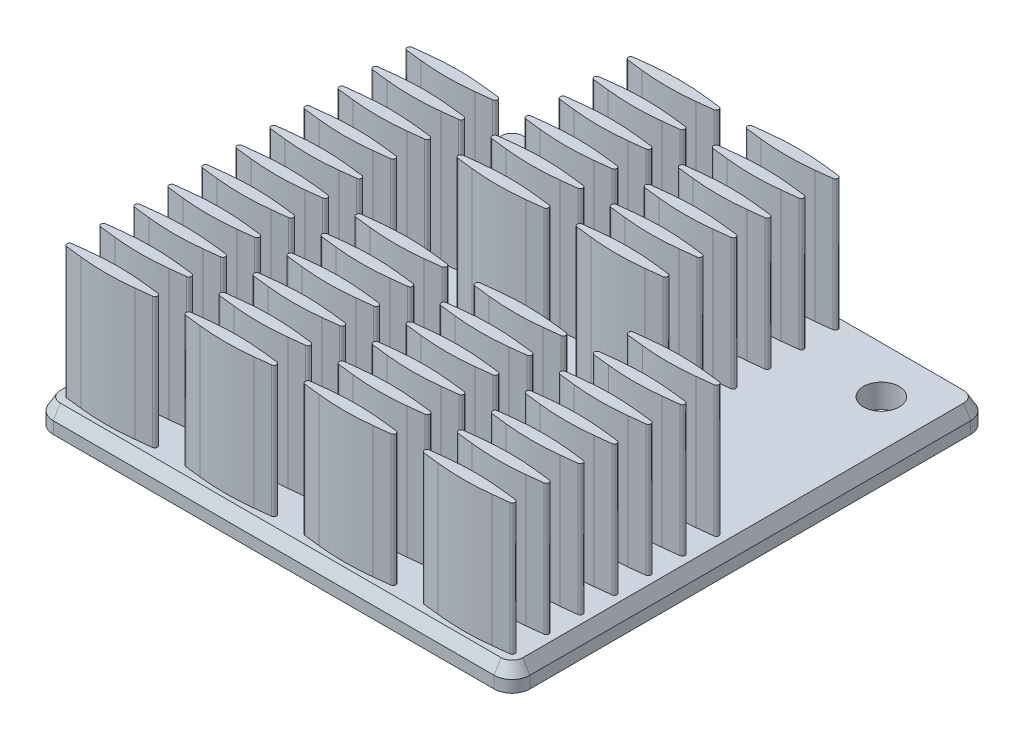
SolidWorks part; units mm, degrees
ref_plane "Front Plane" through (0, 0, 0) normal (0, 0, 1) x (1, 0, 0)
ref_plane "Top Plane" through (0, 0, 0) normal (0, 1, 0) x (1, 0, 0)
ref_plane "Right Plane" through (0, 0, 0) normal (1, 0, 0) x (0, 0, -1)
ref_plane "Plane2" through (0, -39.8348, 0) normal (0, 1, 0) x (1, 0, 0)
sketch "Sketch51" plane through (0, -39.8348, 0) normal (0, 1, 0) x (1, 0, 0)
  line L0 (-325.5822, -856.4267) -> (-325.5822, -896.4267)
  line L1 (-325.5822, -896.4267) -> (-285.5822, -896.4267)
  line L2 (-285.5822, -896.4267) -> (-285.5822, -856.4267)
  line L3 (-285.5822, -856.4267) -> (-325.5822, -856.4267)
extrude "Boss-Extrude44" add sketch "Sketch51" against normal blind 2 separate body
sketch "Sketch52" plane through (0, -39.8348, 0) normal (0, 1, 0) x (-1, 0, 0)
  line L0 (296.9773, 858.0883) -> (300.5822, 858.4992)
  line L1 (300.5822, 858.4992) -> (304.1871, 858.0883)
  line L2 (304.1871, 857.6511) -> (300.5822, 857.2402)
  line L3 (300.5822, 857.2402) -> (296.9773, 857.6511)
  arc A0 (304.1871, 858.0883) -> (304.1871, 857.6511) centre (304.1622, 857.8697) cw
  arc A1 (296.9773, 857.6511) -> (296.9773, 858.0883) centre (297.0022, 857.8697) cw
extrude "Boss-Extrude45" add sketch "Sketch52" along normal blind 11
sketch "Sketch53" plane through (0, -39.8348, 0) normal (0, 1, 0) x (-1, 0, 0)
  line L0 (306.9773, 858.0883) -> (310.5822, 858.4992)
  line L1 (310.5822, 858.4992) -> (314.1871, 858.0883)
  line L2 (314.1871, 857.6511) -> (310.5822, 857.2402)
  line L3 (310.5822, 857.2402) -> (306.9773, 857.6511)
  arc A0 (314.1871, 858.0883) -> (314.1871, 857.6511) centre (314.1622, 857.8697) cw
  arc A1 (306.9773, 857.6511) -> (306.9773, 858.0883) centre (307.0022, 857.8697) cw
extrude "Boss-Extrude46" add sketch "Sketch53" along normal blind 11
sketch "Sketch54" plane through (0, -39.8348, 0) normal (0, 1, 0) x (-1, 0, 0)
  line L0 (296.9773, 860.9433) -> (300.5822, 861.3542)
  line L1 (300.5822, 861.3542) -> (304.1871, 860.9433)
  line L2 (304.1871, 860.5061) -> (300.5822, 860.0952)
  line L3 (300.5822, 860.0952) -> (296.9773, 860.5061)
  arc A0 (304.1871, 860.9433) -> (304.1871, 860.5061) centre (304.1622, 860.7247) cw
  arc A1 (296.9773, 860.5061) -> (296.9773, 860.9433) centre (297.0022, 860.7247) cw
extrude "Boss-Extrude47" add sketch "Sketch54" along normal blind 11
sketch "Sketch55" plane through (0, -39.8348, 0) normal (0, 1, 0) x (-1, 0, 0)
  line L0 (306.9773, 860.9433) -> (310.5822, 861.3542)
  line L1 (310.5822, 861.3542) -> (314.1871, 860.9433)
  line L2 (314.1871, 860.5061) -> (310.5822, 860.0952)
  line L3 (310.5822, 860.0952) -> (306.9773, 860.5061)
  arc A0 (314.1871, 860.9433) -> (314.1871, 860.5061) centre (314.1622, 860.7247) cw
  arc A1 (306.9773, 860.5061) -> (306.9773, 860.9433) centre (307.0022, 860.7247) cw
extrude "Boss-Extrude48" add sketch "Sketch55" along normal blind 11
sketch "Sketch56" plane through (0, -39.8348, 0) normal (0, 1, 0) x (-1, 0, 0)
  line L0 (296.9773, 863.7983) -> (300.5822, 864.2092)
  line L1 (300.5822, 864.2092) -> (304.1871, 863.7983)
  line L2 (304.1871, 863.3611) -> (300.5822, 862.9502)
  line L3 (300.5822, 862.9502) -> (296.9773, 863.3611)
  arc A0 (304.1871, 863.7983) -> (304.1871, 863.3611) centre (304.1622, 863.5797) cw
  arc A1 (296.9773, 863.3611) -> (296.9773, 863.7983) centre (297.0022, 863.5797) cw
extrude "Boss-Extrude49" add sketch "Sketch56" along normal blind 11
sketch "Sketch57" plane through (0, -39.8348, 0) normal (0, 1, 0) x (-1, 0, 0)
  line L0 (306.9773, 863.7983) -> (310.5822, 864.2092)
  line L1 (310.5822, 864.2092) -> (314.1871, 863.7983)
  line L2 (314.1871, 863.3611) -> (310.5822, 862.9502)
  line L3 (310.5822, 862.9502) -> (306.9773, 863.3611)
  arc A0 (314.1871, 863.7983) -> (314.1871, 863.3611) centre (314.1622, 863.5797) cw
  arc A1 (306.9773, 863.3611) -> (306.9773, 863.7983) centre (307.0022, 863.5797) cw
extrude "Boss-Extrude50" add sketch "Sketch57" along normal blind 11
sketch "Sketch58" plane through (0, -39.8348, 0) normal (0, 1, 0) x (-1, 0, 0)
  line L0 (296.9773, 866.6533) -> (300.5822, 867.0642)
  line L1 (300.5822, 867.0642) -> (304.1871, 866.6533)
  line L2 (304.1871, 866.2161) -> (300.5822, 865.8052)
  line L3 (300.5822, 865.8052) -> (296.9773, 866.2161)
  arc A0 (304.1871, 866.6533) -> (304.1871, 866.2161) centre (304.1622, 866.4347) cw
  arc A1 (296.9773, 866.2161) -> (296.9773, 866.6533) centre (297.0022, 866.4347) cw
extrude "Boss-Extrude51" add sketch "Sketch58" along normal blind 11
sketch "Sketch59" plane through (0, -39.8348, 0) normal (0, 1, 0) x (-1, 0, 0)
  line L0 (306.9773, 866.6533) -> (310.5822, 867.0642)
  line L1 (310.5822, 867.0642) -> (314.1871, 866.6533)
  line L2 (314.1871, 866.2161) -> (310.5822, 865.8052)
  line L3 (310.5822, 865.8052) -> (306.9773, 866.2161)
  arc A0 (314.1871, 866.6533) -> (314.1871, 866.2161) centre (314.1622, 866.4347) cw
  arc A1 (306.9773, 866.2161) -> (306.9773, 866.6533) centre (307.0022, 866.4347) cw
extrude "Boss-Extrude52" add sketch "Sketch59" along normal blind 11
sketch "Sketch60" plane through (0, -39.8348, 0) normal (0, 1, 0) x (-1, 0, 0)
  line L0 (316.9773, 866.6533) -> (320.5822, 867.0642)
  line L1 (320.5822, 867.0642) -> (324.1871, 866.6533)
  line L2 (324.1871, 866.2161) -> (320.5822, 865.8052)
  line L3 (320.5822, 865.8052) -> (316.9773, 866.2161)
  arc A0 (324.1871, 866.6533) -> (324.1871, 866.2161) centre (324.1622, 866.4347) cw
  arc A1 (316.9773, 866.2161) -> (316.9773, 866.6533) centre (317.0022, 866.4347) cw
extrude "Boss-Extrude53" add sketch "Sketch60" along normal blind 11
sketch "Sketch61" plane through (0, -39.8348, 0) normal (0, 1, 0) x (-1, 0, 0)
  line L0 (296.9773, 869.5083) -> (300.5822, 869.9192)
  line L1 (300.5822, 869.9192) -> (304.1871, 869.5083)
  line L2 (304.1871, 869.0711) -> (300.5822, 868.6602)
  line L3 (300.5822, 868.6602) -> (296.9773, 869.0711)
  arc A0 (304.1871, 869.5083) -> (304.1871, 869.0711) centre (304.1622, 869.2897) cw
  arc A1 (296.9773, 869.0711) -> (296.9773, 869.5083) centre (297.0022, 869.2897) cw
extrude "Boss-Extrude54" add sketch "Sketch61" along normal blind 11
sketch "Sketch62" plane through (0, -39.8348, 0) normal (0, 1, 0) x (-1, 0, 0)
  line L0 (306.9773, 869.5083) -> (310.5822, 869.9192)
  line L1 (310.5822, 869.9192) -> (314.1871, 869.5083)
  line L2 (314.1871, 869.0711) -> (310.5822, 868.6602)
  line L3 (310.5822, 868.6602) -> (306.9773, 869.0711)
  arc A0 (314.1871, 869.5083) -> (314.1871, 869.0711) centre (314.1622, 869.2897) cw
  arc A1 (306.9773, 869.0711) -> (306.9773, 869.5083) centre (307.0022, 869.2897) cw
extrude "Boss-Extrude55" add sketch "Sketch62" along normal blind 11
sketch "Sketch63" plane through (0, -39.8348, 0) normal (0, 1, 0) x (-1, 0, 0)
  line L0 (316.9773, 869.5083) -> (320.5822, 869.9192)
  line L1 (320.5822, 869.9192) -> (324.1871, 869.5083)
  line L2 (324.1871, 869.0711) -> (320.5822, 868.6602)
  line L3 (320.5822, 868.6602) -> (316.9773, 869.0711)
  arc A0 (324.1871, 869.5083) -> (324.1871, 869.0711) centre (324.1622, 869.2897) cw
  arc A1 (316.9773, 869.0711) -> (316.9773, 869.5083) centre (317.0022, 869.2897) cw
extrude "Boss-Extrude56" add sketch "Sketch63" along normal blind 11
sketch "Sketch64" plane through (0, -39.8348, 0) normal (0, 1, 0) x (-1, 0, 0)
  line L0 (296.9773, 872.3633) -> (300.5822, 872.7742)
  line L1 (300.5822, 872.7742) -> (304.1871, 872.3633)
  line L2 (304.1871, 871.9261) -> (300.5822, 871.5152)
  line L3 (300.5822, 871.5152) -> (296.9773, 871.9261)
  arc A0 (304.1871, 872.3633) -> (304.1871, 871.9261) centre (304.1622, 872.1447) cw
  arc A1 (296.9773, 871.9261) -> (296.9773, 872.3633) centre (297.0022, 872.1447) cw
extrude "Boss-Extrude57" add sketch "Sketch64" along normal blind 11
sketch "Sketch65" plane through (0, -39.8348, 0) normal (0, 1, 0) x (-1, 0, 0)
  line L0 (306.9773, 872.3633) -> (310.5822, 872.7742)
  line L1 (310.5822, 872.7742) -> (314.1871, 872.3633)
  line L2 (314.1871, 871.9261) -> (310.5822, 871.5152)
  line L3 (310.5822, 871.5152) -> (306.9773, 871.9261)
  arc A0 (314.1871, 872.3633) -> (314.1871, 871.9261) centre (314.1622, 872.1447) cw
  arc A1 (306.9773, 871.9261) -> (306.9773, 872.3633) centre (307.0022, 872.1447) cw
extrude "Boss-Extrude58" add sketch "Sketch65" along normal blind 11
sketch "Sketch66" plane through (0, -39.8348, 0) normal (0, 1, 0) x (-1, 0, 0)
  line L0 (316.9773, 872.3633) -> (320.5822, 872.7742)
  line L1 (320.5822, 872.7742) -> (324.1871, 872.3633)
  line L2 (324.1871, 871.9261) -> (320.5822, 871.5152)
  line L3 (320.5822, 871.5152) -> (316.9773, 871.9261)
  arc A0 (324.1871, 872.3633) -> (324.1871, 871.9261) centre (324.1622, 872.1447) cw
  arc A1 (316.9773, 871.9261) -> (316.9773, 872.3633) centre (317.0022, 872.1447) cw
extrude "Boss-Extrude59" add sketch "Sketch66" along normal blind 11
sketch "Sketch67" plane through (0, -39.8348, 0) normal (0, 1, 0) x (-1, 0, 0)
  line L0 (316.9773, 875.2183) -> (320.5822, 875.6292)
  line L1 (320.5822, 875.6292) -> (324.1871, 875.2183)
  line L2 (324.1871, 874.7811) -> (320.5822, 874.3702)
  line L3 (320.5822, 874.3702) -> (316.9773, 874.7811)
  arc A0 (324.1871, 875.2183) -> (324.1871, 874.7811) centre (324.1622, 874.9997) cw
  arc A1 (316.9773, 874.7811) -> (316.9773, 875.2183) centre (317.0022, 874.9997) cw
extrude "Boss-Extrude60" add sketch "Sketch67" along normal blind 11
sketch "Sketch68" plane through (0, -39.8348, 0) normal (0, 1, 0) x (-1, 0, 0)
  line L0 (286.9773, 878.0733) -> (290.5822, 878.4842)
  line L1 (290.5822, 878.4842) -> (294.1871, 878.0733)
  line L2 (294.1871, 877.6361) -> (290.5822, 877.2252)
  line L3 (290.5822, 877.2252) -> (286.9773, 877.6361)
  arc A0 (294.1871, 878.0733) -> (294.1871, 877.6361) centre (294.1622, 877.8547) cw
  arc A1 (286.9773, 877.6361) -> (286.9773, 878.0733) centre (287.0022, 877.8547) cw
extrude "Boss-Extrude61" add sketch "Sketch68" along normal blind 11
sketch "Sketch69" plane through (0, -39.8348, 0) normal (0, 1, 0) x (-1, 0, 0)
  line L0 (316.9773, 878.0733) -> (320.5822, 878.4842)
  line L1 (320.5822, 878.4842) -> (324.1871, 878.0733)
  line L2 (324.1871, 877.6361) -> (320.5822, 877.2252)
  line L3 (320.5822, 877.2252) -> (316.9773, 877.6361)
  arc A0 (324.1871, 878.0733) -> (324.1871, 877.6361) centre (324.1622, 877.8547) cw
  arc A1 (316.9773, 877.6361) -> (316.9773, 878.0733) centre (317.0022, 877.8547) cw
extrude "Boss-Extrude62" add sketch "Sketch69" along normal blind 11
sketch "Sketch70" plane through (0, -39.8348, 0) normal (0, 1, 0) x (-1, 0, 0)
  line L0 (286.9773, 880.9283) -> (290.5822, 881.3392)
  line L1 (290.5822, 881.3392) -> (294.1871, 880.9283)
  line L2 (294.1871, 880.4911) -> (290.5822, 880.0802)
  line L3 (290.5822, 880.0802) -> (286.9773, 880.4911)
  arc A0 (294.1871, 880.9283) -> (294.1871, 880.4911) centre (294.1622, 880.7097) cw
  arc A1 (286.9773, 880.4911) -> (286.9773, 880.9283) centre (287.0022, 880.7097) cw
extrude "Boss-Extrude63" add sketch "Sketch70" along normal blind 11
sketch "Sketch71" plane through (0, -39.8348, 0) normal (0, 1, 0) x (-1, 0, 0)
  line L0 (296.9773, 880.9283) -> (300.5822, 881.3392)
  line L1 (300.5822, 881.3392) -> (304.1871, 880.9283)
  line L2 (304.1871, 880.4911) -> (300.5822, 880.0802)
  line L3 (300.5822, 880.0802) -> (296.9773, 880.4911)
  arc A0 (304.1871, 880.9283) -> (304.1871, 880.4911) centre (304.1622, 880.7097) cw
  arc A1 (296.9773, 880.4911) -> (296.9773, 880.9283) centre (297.0022, 880.7097) cw
extrude "Boss-Extrude64" add sketch "Sketch71" along normal blind 11
sketch "Sketch72" plane through (0, -39.8348, 0) normal (0, 1, 0) x (-1, 0, 0)
  line L0 (306.9773, 880.9283) -> (310.5822, 881.3392)
  line L1 (310.5822, 881.3392) -> (314.1871, 880.9283)
  line L2 (314.1871, 880.4911) -> (310.5822, 880.0802)
  line L3 (310.5822, 880.0802) -> (306.9773, 880.4911)
  arc A0 (314.1871, 880.9283) -> (314.1871, 880.4911) centre (314.1622, 880.7097) cw
  arc A1 (306.9773, 880.4911) -> (306.9773, 880.9283) centre (307.0022, 880.7097) cw
extrude "Boss-Extrude65" add sketch "Sketch72" along normal blind 11
sketch "Sketch73" plane through (0, -39.8348, 0) normal (0, 1, 0) x (-1, 0, 0)
  line L0 (316.9773, 880.9283) -> (320.5822, 881.3392)
  line L1 (320.5822, 881.3392) -> (324.1871, 880.9283)
  line L2 (324.1871, 880.4911) -> (320.5822, 880.0802)
  line L3 (320.5822, 880.0802) -> (316.9773, 880.4911)
  arc A0 (324.1871, 880.9283) -> (324.1871, 880.4911) centre (324.1622, 880.7097) cw
  arc A1 (316.9773, 880.4911) -> (316.9773, 880.9283) centre (317.0022, 880.7097) cw
extrude "Boss-Extrude66" add sketch "Sketch73" along normal blind 11
sketch "Sketch74" plane through (0, -39.8348, 0) normal (0, 1, 0) x (-1, 0, 0)
  line L0 (286.9773, 883.7833) -> (290.5822, 884.1942)
  line L1 (290.5822, 884.1942) -> (294.1871, 883.7833)
  line L2 (294.1871, 883.3461) -> (290.5822, 882.9352)
  line L3 (290.5822, 882.9352) -> (286.9773, 883.3461)
  arc A0 (294.1871, 883.7833) -> (294.1871, 883.3461) centre (294.1622, 883.5647) cw
  arc A1 (286.9773, 883.3461) -> (286.9773, 883.7833) centre (287.0022, 883.5647) cw
extrude "Boss-Extrude67" add sketch "Sketch74" along normal blind 11
sketch "Sketch75" plane through (0, -39.8348, 0) normal (0, 1, 0) x (-1, 0, 0)
  line L0 (296.9773, 883.7833) -> (300.5822, 884.1942)
  line L1 (300.5822, 884.1942) -> (304.1871, 883.7833)
  line L2 (304.1871, 883.3461) -> (300.5822, 882.9352)
  line L3 (300.5822, 882.9352) -> (296.9773, 883.3461)
  arc A0 (304.1871, 883.7833) -> (304.1871, 883.3461) centre (304.1622, 883.5647) cw
  arc A1 (296.9773, 883.3461) -> (296.9773, 883.7833) centre (297.0022, 883.5647) cw
extrude "Boss-Extrude68" add sketch "Sketch75" along normal blind 11
sketch "Sketch76" plane through (0, -39.8348, 0) normal (0, 1, 0) x (-1, 0, 0)
  line L0 (306.9773, 883.7833) -> (310.5822, 884.1942)
  line L1 (310.5822, 884.1942) -> (314.1871, 883.7833)
  line L2 (314.1871, 883.3461) -> (310.5822, 882.9352)
  line L3 (310.5822, 882.9352) -> (306.9773, 883.3461)
  arc A0 (314.1871, 883.7833) -> (314.1871, 883.3461) centre (314.1622, 883.5647) cw
  arc A1 (306.9773, 883.3461) -> (306.9773, 883.7833) centre (307.0022, 883.5647) cw
extrude "Boss-Extrude69" add sketch "Sketch76" along normal blind 11
sketch "Sketch77" plane through (0, -39.8348, 0) normal (0, 1, 0) x (-1, 0, 0)
  line L0 (316.9773, 883.7833) -> (320.5822, 884.1942)
  line L1 (320.5822, 884.1942) -> (324.1871, 883.7833)
  line L2 (324.1871, 883.3461) -> (320.5822, 882.9352)
  line L3 (320.5822, 882.9352) -> (316.9773, 883.3461)
  arc A0 (324.1871, 883.7833) -> (324.1871, 883.3461) centre (324.1622, 883.5647) cw
  arc A1 (316.9773, 883.3461) -> (316.9773, 883.7833) centre (317.0022, 883.5647) cw
extrude "Boss-Extrude70" add sketch "Sketch77" along normal blind 11
sketch "Sketch78" plane through (0, -39.8348, 0) normal (0, 1, 0) x (-1, 0, 0)
  line L0 (286.9773, 886.6383) -> (290.5822, 887.0492)
  line L1 (290.5822, 887.0492) -> (294.1871, 886.6383)
  line L2 (294.1871, 886.2011) -> (290.5822, 885.7902)
  line L3 (290.5822, 885.7902) -> (286.9773, 886.2011)
  arc A0 (294.1871, 886.6383) -> (294.1871, 886.2011) centre (294.1622, 886.4197) cw
  arc A1 (286.9773, 886.2011) -> (286.9773, 886.6383) centre (287.0022, 886.4197) cw
extrude "Boss-Extrude71" add sketch "Sketch78" along normal blind 11
sketch "Sketch79" plane through (0, -39.8348, 0) normal (0, 1, 0) x (-1, 0, 0)
  line L0 (296.9773, 886.6383) -> (300.5822, 887.0492)
  line L1 (300.5822, 887.0492) -> (304.1871, 886.6383)
  line L2 (304.1871, 886.2011) -> (300.5822, 885.7902)
  line L3 (300.5822, 885.7902) -> (296.9773, 886.2011)
  arc A0 (304.1871, 886.6383) -> (304.1871, 886.2011) centre (304.1622, 886.4197) cw
  arc A1 (296.9773, 886.2011) -> (296.9773, 886.6383) centre (297.0022, 886.4197) cw
extrude "Boss-Extrude72" add sketch "Sketch79" along normal blind 11
sketch "Sketch80" plane through (0, -39.8348, 0) normal (0, 1, 0) x (-1, 0, 0)
  line L0 (306.9773, 886.6383) -> (310.5822, 887.0492)
  line L1 (310.5822, 887.0492) -> (314.1871, 886.6383)
  line L2 (314.1871, 886.2011) -> (310.5822, 885.7902)
  line L3 (310.5822, 885.7902) -> (306.9773, 886.2011)
  arc A0 (314.1871, 886.6383) -> (314.1871, 886.2011) centre (314.1622, 886.4197) cw
  arc A1 (306.9773, 886.2011) -> (306.9773, 886.6383) centre (307.0022, 886.4197) cw
extrude "Boss-Extrude73" add sketch "Sketch80" along normal blind 11
sketch "Sketch81" plane through (0, -39.8348, 0) normal (0, 1, 0) x (-1, 0, 0)
  line L0 (316.9773, 886.6383) -> (320.5822, 887.0492)
  line L1 (320.5822, 887.0492) -> (324.1871, 886.6383)
  line L2 (324.1871, 886.2011) -> (320.5822, 885.7902)
  line L3 (320.5822, 885.7902) -> (316.9773, 886.2011)
  arc A0 (324.1871, 886.6383) -> (324.1871, 886.2011) centre (324.1622, 886.4197) cw
  arc A1 (316.9773, 886.2011) -> (316.9773, 886.6383) centre (317.0022, 886.4197) cw
extrude "Boss-Extrude74" add sketch "Sketch81" along normal blind 11
sketch "Sketch82" plane through (0, -39.8348, 0) normal (0, 1, 0) x (-1, 0, 0)
  line L0 (286.9773, 889.4933) -> (290.5822, 889.9042)
  line L1 (290.5822, 889.9042) -> (294.1871, 889.4933)
  line L2 (294.1871, 889.0561) -> (290.5822, 888.6452)
  line L3 (290.5822, 888.6452) -> (286.9773, 889.0561)
  arc A0 (294.1871, 889.4933) -> (294.1871, 889.0561) centre (294.1622, 889.2747) cw
  arc A1 (286.9773, 889.0561) -> (286.9773, 889.4933) centre (287.0022, 889.2747) cw
extrude "Boss-Extrude75" add sketch "Sketch82" along normal blind 11
sketch "Sketch83" plane through (0, -39.8348, 0) normal (0, 1, 0) x (-1, 0, 0)
  line L0 (296.9773, 889.4933) -> (300.5822, 889.9042)
  line L1 (300.5822, 889.9042) -> (304.1871, 889.4933)
  line L2 (304.1871, 889.0561) -> (300.5822, 888.6452)
  line L3 (300.5822, 888.6452) -> (296.9773, 889.0561)
  arc A0 (304.1871, 889.4933) -> (304.1871, 889.0561) centre (304.1622, 889.2747) cw
  arc A1 (296.9773, 889.0561) -> (296.9773, 889.4933) centre (297.0022, 889.2747) cw
extrude "Boss-Extrude76" add sketch "Sketch83" along normal blind 11
sketch "Sketch84" plane through (0, -39.8348, 0) normal (0, 1, 0) x (-1, 0, 0)
  line L0 (306.9773, 889.4933) -> (310.5822, 889.9042)
  line L1 (310.5822, 889.9042) -> (314.1871, 889.4933)
  line L2 (314.1871, 889.0561) -> (310.5822, 888.6452)
  line L3 (310.5822, 888.6452) -> (306.9773, 889.0561)
  arc A0 (314.1871, 889.4933) -> (314.1871, 889.0561) centre (314.1622, 889.2747) cw
  arc A1 (306.9773, 889.0561) -> (306.9773, 889.4933) centre (307.0022, 889.2747) cw
extrude "Boss-Extrude77" add sketch "Sketch84" along normal blind 11
sketch "Sketch85" plane through (0, -39.8348, 0) normal (0, 1, 0) x (-1, 0, 0)
  line L0 (316.9773, 889.4933) -> (320.5822, 889.9042)
  line L1 (320.5822, 889.9042) -> (324.1871, 889.4933)
  line L2 (324.1871, 889.0561) -> (320.5822, 888.6452)
  line L3 (320.5822, 888.6452) -> (316.9773, 889.0561)
  arc A0 (324.1871, 889.4933) -> (324.1871, 889.0561) centre (324.1622, 889.2747) cw
  arc A1 (316.9773, 889.0561) -> (316.9773, 889.4933) centre (317.0022, 889.2747) cw
extrude "Boss-Extrude78" add sketch "Sketch85" along normal blind 11
sketch "Sketch86" plane through (0, -39.8348, 0) normal (0, 1, 0) x (-1, 0, 0)
  line L0 (286.9773, 892.3483) -> (290.5822, 892.7592)
  line L1 (290.5822, 892.7592) -> (294.1871, 892.3483)
  line L2 (294.1871, 891.9111) -> (290.5822, 891.5002)
  line L3 (290.5822, 891.5002) -> (286.9773, 891.9111)
  arc A0 (294.1871, 892.3483) -> (294.1871, 891.9111) centre (294.1622, 892.1297) cw
  arc A1 (286.9773, 891.9111) -> (286.9773, 892.3483) centre (287.0022, 892.1297) cw
extrude "Boss-Extrude79" add sketch "Sketch86" along normal blind 11
sketch "Sketch87" plane through (0, -39.8348, 0) normal (0, 1, 0) x (-1, 0, 0)
  line L0 (296.9773, 892.3483) -> (300.5822, 892.7592)
  line L1 (300.5822, 892.7592) -> (304.1871, 892.3483)
  line L2 (304.1871, 891.9111) -> (300.5822, 891.5002)
  line L3 (300.5822, 891.5002) -> (296.9773, 891.9111)
  arc A0 (304.1871, 892.3483) -> (304.1871, 891.9111) centre (304.1622, 892.1297) cw
  arc A1 (296.9773, 891.9111) -> (296.9773, 892.3483) centre (297.0022, 892.1297) cw
extrude "Boss-Extrude80" add sketch "Sketch87" along normal blind 11
sketch "Sketch88" plane through (0, -39.8348, 0) normal (0, 1, 0) x (-1, 0, 0)
  line L0 (306.9773, 892.3483) -> (310.5822, 892.7592)
  line L1 (310.5822, 892.7592) -> (314.1871, 892.3483)
  line L2 (314.1871, 891.9111) -> (310.5822, 891.5002)
  line L3 (310.5822, 891.5002) -> (306.9773, 891.9111)
  arc A0 (314.1871, 892.3483) -> (314.1871, 891.9111) centre (314.1622, 892.1297) cw
  arc A1 (306.9773, 891.9111) -> (306.9773, 892.3483) centre (307.0022, 892.1297) cw
extrude "Boss-Extrude81" add sketch "Sketch88" along normal blind 11
sketch "Sketch89" plane through (0, -39.8348, 0) normal (0, 1, 0) x (-1, 0, 0)
  line L0 (316.9773, 892.3483) -> (320.5822, 892.7592)
  line L1 (320.5822, 892.7592) -> (324.1871, 892.3483)
  line L2 (324.1871, 891.9111) -> (320.5822, 891.5002)
  line L3 (320.5822, 891.5002) -> (316.9773, 891.9111)
  arc A0 (324.1871, 892.3483) -> (324.1871, 891.9111) centre (324.1622, 892.1297) cw
  arc A1 (316.9773, 891.9111) -> (316.9773, 892.3483) centre (317.0022, 892.1297) cw
extrude "Boss-Extrude82" add sketch "Sketch89" along normal blind 11
sketch "Sketch90" plane through (0, -39.8348, 0) normal (0, 1, 0) x (-1, 0, 0)
  line L0 (286.9773, 895.2033) -> (290.5822, 895.6142)
  line L1 (290.5822, 895.6142) -> (294.1871, 895.2033)
  line L2 (294.1871, 894.7661) -> (290.5822, 894.3552)
  line L3 (290.5822, 894.3552) -> (286.9773, 894.7661)
  arc A0 (294.1871, 895.2033) -> (294.1871, 894.7661) centre (294.1622, 894.9847) cw
  arc A1 (286.9773, 894.7661) -> (286.9773, 895.2033) centre (287.0022, 894.9847) cw
extrude "Boss-Extrude83" add sketch "Sketch90" along normal blind 11
sketch "Sketch91" plane through (0, -39.8348, 0) normal (0, 1, 0) x (-1, 0, 0)
  line L0 (296.9773, 895.2033) -> (300.5822, 895.6142)
  line L1 (300.5822, 895.6142) -> (304.1871, 895.2033)
  line L2 (304.1871, 894.7661) -> (300.5822, 894.3552)
  line L3 (300.5822, 894.3552) -> (296.9773, 894.7661)
  arc A0 (304.1871, 895.2033) -> (304.1871, 894.7661) centre (304.1622, 894.9847) cw
  arc A1 (296.9773, 894.7661) -> (296.9773, 895.2033) centre (297.0022, 894.9847) cw
extrude "Boss-Extrude84" add sketch "Sketch91" along normal blind 11
sketch "Sketch92" plane through (0, -39.8348, 0) normal (0, 1, 0) x (-1, 0, 0)
  line L0 (306.9773, 895.2033) -> (310.5822, 895.6142)
  line L1 (310.5822, 895.6142) -> (314.1871, 895.2033)
  line L2 (314.1871, 894.7661) -> (310.5822, 894.3552)
  line L3 (310.5822, 894.3552) -> (306.9773, 894.7661)
  arc A0 (314.1871, 895.2033) -> (314.1871, 894.7661) centre (314.1622, 894.9847) cw
  arc A1 (306.9773, 894.7661) -> (306.9773, 895.2033) centre (307.0022, 894.9847) cw
extrude "Boss-Extrude85" add sketch "Sketch92" along normal blind 11
sketch "Sketch93" plane through (0, -39.8348, 0) normal (0, 1, 0) x (-1, 0, 0)
  line L0 (316.9773, 895.2033) -> (320.5822, 895.6142)
  line L1 (320.5822, 895.6142) -> (324.1871, 895.2033)
  line L2 (324.1871, 894.7661) -> (320.5822, 894.3552)
  line L3 (320.5822, 894.3552) -> (316.9773, 894.7661)
  arc A0 (324.1871, 895.2033) -> (324.1871, 894.7661) centre (324.1622, 894.9847) cw
  arc A1 (316.9773, 894.7661) -> (316.9773, 895.2033) centre (317.0022, 894.9847) cw
extrude "Boss-Extrude86" add sketch "Sketch93" along normal blind 11
hole_wizard "Ø6.0 (6) Diameter Hole2" positions "Sketch95" profile "Sketch94" hole size "Ø6.0" standard "ANSI Metric"
sketch "Sketch95" plane through (0, -39.8348, 0) normal (0, 1, 0) x (1, 0, 0)
  point P0 (-305.5822, -876.4267)
sketch "Sketch94" plane through (-305.5822, -39.8348, 876.4267) normal (1, 0, 0) x (0, 0, 1)
  line L0 (0, 0) -> (0, 2)
  line L1 (0, 2) -> (3, 2)
  line L2 (3, 2) -> (3, 0)
  line L5 (3, 0) -> (0, 0)
  line L11 (0, -6.35) -> (0, 107.95) construction
  dimension "Thru Hole Dia." = 6
  dimension "Thru Hole Depth" = 2
hole_wizard "Ø3.0 (3) Diameter Hole2" positions "Sketch97" profile "Sketch96" hole size "Ø3.0" standard "ANSI Metric"
sketch "Sketch97" plane through (0, -39.8348, 0) normal (0, 1, 0) x (1, 0, 0)
  point P0 (-290.0822, -860.9267)
  point P1 (-321.0822, -860.9267)
sketch "Sketch96" plane through (-290.0822, -39.8348, 860.9267) normal (1, 0, 0) x (0, 0, 1)
  line L0 (0, 0) -> (0, 2)
  line L1 (0, 2) -> (1.5, 2)
  line L2 (1.5, 2) -> (1.5, 0)
  line L5 (1.5, 0) -> (0, 0)
  line L11 (0, -6.35) -> (0, 107.95) construction
  dimension "Thru Hole Dia." = 3
  dimension "Thru Hole Depth" = 2
fillet "Fillet3" radius 1.5 4 edges at (-325.5822, -40.8348, 896.4267) (-325.5822, -40.8348, 856.4267) (-285.5822, -40.8348, 896.4267) (-285.5822, -40.8348, 856.4267) tangent propagation no
chamfer "Chamfer2" distance 0.5774 angle 60 8 edges at (-286.0216, -39.8348, 856.866) (-285.5822, -39.8348, 876.4267) (-305.5822, -39.8348, 856.4267) (-286.0216, -39.8348, 895.9874) (-325.1429, -39.8348, 856.866) (-305.5822, -39.8348, 896.4267) (-325.5822, -39.8348, 876.4267) (-325.1429, -39.8348, 895.9874) first distance on face at (-290.0822, -39.8348, 862.4267)
fillet "Fillet4" radius 20 84 edges at (-300.5822, -34.3348, 888.6452) (-300.5822, -34.3348, 882.9352) (-300.5822, -34.3348, 894.3552) (-300.5822, -34.3348, 858.4992) (-300.5822, -34.3348, 885.7902) (-300.5822, -34.3348, 857.2402) (-300.5822, -34.3348, 891.5002) (-310.5822, -34.3348, 858.4992) (-320.5822, -34.3348, 880.0802) (-310.5822, -34.3348, 857.2402) (-320.5822, -34.3348, 882.9352) (-300.5822, -34.3348, 861.3542) (-320.5822, -34.3348, 885.7902) (-300.5822, -34.3348, 860.0952) (-320.5822, -34.3348, 888.6452) (-310.5822, -34.3348, 861.3542) (-320.5822, -34.3348, 891.5002) (-310.5822, -34.3348, 860.0952) (-320.5822, -34.3348, 894.3552) (-300.5822, -34.3348, 864.2092) (-290.5822, -34.3348, 882.9352) (-300.5822, -34.3348, 862.9502) (-310.5822, -34.3348, 882.9352) (-310.5822, -34.3348, 864.2092) (-290.5822, -34.3348, 885.7902) (-310.5822, -34.3348, 862.9502) (-310.5822, -34.3348, 885.7902) (-300.5822, -34.3348, 867.0642) (-290.5822, -34.3348, 888.6452) (-300.5822, -34.3348, 865.8052) (-310.5822, -34.3348, 888.6452) (-310.5822, -34.3348, 867.0642) (-290.5822, -34.3348, 891.5002) (-310.5822, -34.3348, 865.8052) (-310.5822, -34.3348, 891.5002) (-320.5822, -34.3348, 867.0642) (-290.5822, -34.3348, 894.3552) (-320.5822, -34.3348, 865.8052) (-310.5822, -34.3348, 894.3552) (-300.5822, -34.3348, 869.9192) (-320.5822, -34.3348, 881.3392) (-300.5822, -34.3348, 868.6602) (-290.5822, -34.3348, 884.1942) (-310.5822, -34.3348, 869.9192) (-300.5822, -34.3348, 884.1942) (-310.5822, -34.3348, 868.6602) (-310.5822, -34.3348, 884.1942) (-320.5822, -34.3348, 869.9192) (-320.5822, -34.3348, 884.1942) (-320.5822, -34.3348, 868.6602) (-290.5822, -34.3348, 887.0492) (-300.5822, -34.3348, 872.7742) (-300.5822, -34.3348, 887.0492) (-300.5822, -34.3348, 871.5152) (-310.5822, -34.3348, 887.0492) (-310.5822, -34.3348, 872.7742) (-320.5822, -34.3348, 887.0492) (-310.5822, -34.3348, 871.5152) (-290.5822, -34.3348, 889.9042) (-320.5822, -34.3348, 872.7742) (-300.5822, -34.3348, 889.9042) (-320.5822, -34.3348, 871.5152) (-310.5822, -34.3348, 889.9042) (-320.5822, -34.3348, 875.6292) (-320.5822, -34.3348, 889.9042) (-320.5822, -34.3348, 874.3702) (-290.5822, -34.3348, 892.7592) (-290.5822, -34.3348, 878.4842) (-300.5822, -34.3348, 892.7592) (-290.5822, -34.3348, 877.2252) (-310.5822, -34.3348, 892.7592) (-320.5822, -34.3348, 878.4842) (-320.5822, -34.3348, 892.7592) (-320.5822, -34.3348, 877.2252) (-290.5822, -34.3348, 895.6142) (-290.5822, -34.3348, 881.3392) (-300.5822, -34.3348, 895.6142) (-290.5822, -34.3348, 880.0802) (-310.5822, -34.3348, 895.6142) (-300.5822, -34.3348, 881.3392) (-320.5822, -34.3348, 895.6142) (-310.5822, -34.3348, 881.3392) (-310.5822, -34.3348, 880.0802) (-300.5822, -34.3348, 880.0802) tangent propagation no
